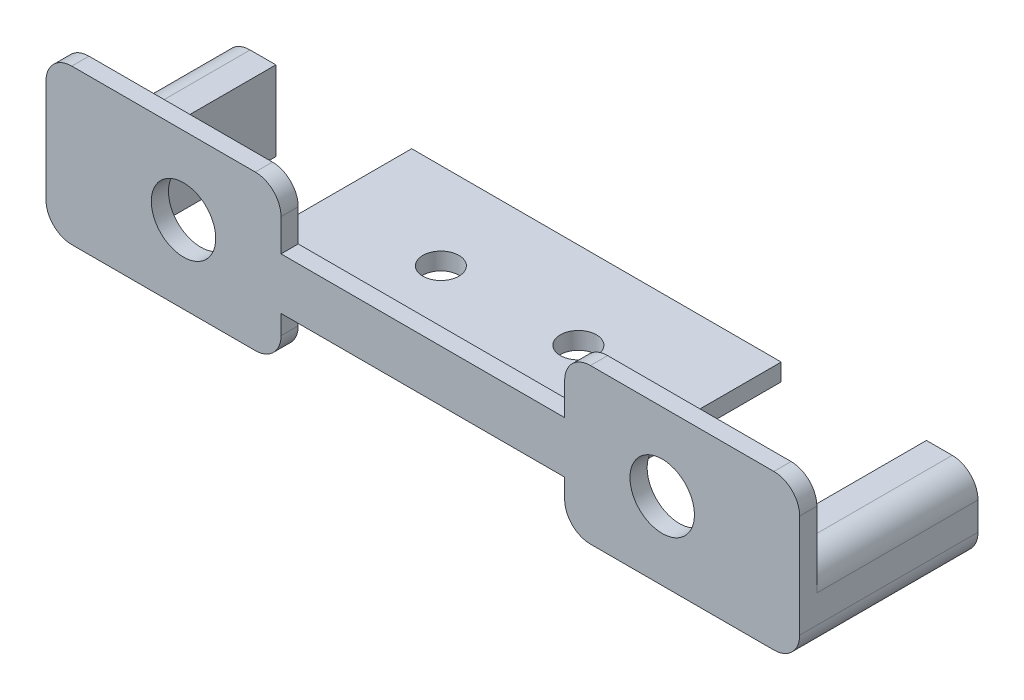
SolidWorks part; units mm, degrees
ref_plane "Front Plane" through (0, 0, 0) normal (0, 0, 1) x (1, 0, 0)
ref_plane "Top Plane" through (0, 0, 0) normal (0, 1, 0) x (1, 0, 0)
ref_plane "Right Plane" through (0, 0, 0) normal (1, 0, 0) x (0, 0, -1)
sketch "Sketch3" plane through (0, 0, 0) normal (0, 1, 0) x (1, 0, 0)
  line L1 (-21.5, 0) -> (21.5, 0)
  line L2 (-21.5, 0) -> (-21.5, 18.2)
  line L3 (-21.5, 18.2) -> (21.5, 18.2)
  line L4 (21.5, 0) -> (21.5, 18.2)
  line L5 (-8, 8.1) -> (8, 8.1) construction
  circle A0 centre (-8, 8.1) radius 2.1
  circle A1 centre (8, 8.1) radius 2.1
  point P6 (0, 0)
  point P12 (0, 8.1)
  dimension "D2" = 4.2
  dimension "D1" = 16
  dimension "D3" = 8
  dimension "D4" = 6
  dimension "D5" = 43
extrude "Boss-Extrude5" add sketch "Sketch3" against normal blind 2 separate body
sketch "Sketch1" plane through (0, 0, 0) normal (0, 0, 1) x (1, 0, 0)
  line L0 (0, -1000) -> (0, 49000) construction
  line L1 (-43.85, -9.25) -> (-16.5, -9.25)
  line L2 (-43.85, -9.25) -> (-43.85, 8.75)
  line L4 (43.85, -9.25) -> (43.85, 8.75)
  line L5 (-43.85, -0.25) -> (43.85, -0.25) construction
  line L6 (-43.85, 8.75) -> (-16.5, 8.75)
  line L15 (-37.85, -24) -> (-37.85, 0) construction
  line L16 (-16.5, 8.75) -> (-16.5, 2)
  line L17 (-16.5, -9.25) -> (-16.5, -4)
  line L18 (-16.5, -4) -> (16.5, -4)
  line L19 (16.5, -4) -> (16.5, -9.25)
  line L20 (16.5, -9.25) -> (43.85, -9.25)
  line L21 (-16.5, 2) -> (16.5, 2)
  line L22 (-21.5, -2) -> (21.5, -2) construction
  line L23 (-21.5, 0) -> (21.5, 0) construction
  line L24 (-21.5, -2) -> (-21.5, 0) construction
  line L25 (16.5, 2) -> (16.5, 8.75)
  line L26 (16.5, 8.75) -> (43.85, 8.75)
  circle A0 centre (-27.85, -0.25) radius 3.75
  circle A2 centre (27.85, -0.25) radius 3.75
  point P14 (0, -4)
  point P28 (-16.5, 1.9721)
  point P31 (-17.976, 1.614)
  point P32 (0, 2)
  dimension "D3" = 7.5
  dimension "D4" = 10
  dimension "D1" = 18
  dimension "D2" = 6
  dimension "D5" = 5
  dimension "D6" = 2
  dimension "D7" = 4
  dimension "D8" = 5
  dimension "D9" = 2
extrude "Boss-Extrude1" add sketch "Sketch1" along normal blind 2
chamfer "Chamfer1" distance 1.5 angle 45 1 edges at (0, -2, 0)
sketch "Sketch5" plane through (0, 0, 0) normal (0, 0, -1) x (-1, 0, 0)
  line L0 (43.85, -9.25) -> (16.5, -9.25) construction
  line L1 (43.85, 0) -> (37.85, 0)
  line L2 (43.85, 0) -> (43.85, -9.25)
  line L3 (43.85, -9.25) -> (37.85, -9.25)
  line L4 (37.85, 0) -> (37.85, -9.25)
  line L5 (37.85, -24) -> (37.85, 0) construction
  line L6 (37.85, 0) -> (60.85, 0) construction
extrude "Boss-Extrude4" add sketch "Sketch5" along normal up to surface (18.75 mm away)
mirror "Mirror2" about plane through (0, 0, 0) normal (1, 0, 0) of "Boss-Extrude4"
fillet "Fillet1" radius 3 10 edges at (-43.85, -9.25, -8.375) (-43.85, 8.75, 1) (-43.85, 0, -9.375) (43.85, 0, -9.375) (43.85, -9.25, -8.375) (43.85, 8.75, 1) (16.5, -9.25, 1) (16.5, 8.75, 1) (-16.5, 8.75, 1) (-16.5, -9.25, 1)
equation "\"width\"= 24"
equation "\"thk\"= 3"
equation "\"holesize\"= 4.2"
equation "\"holedistance\"= ( 20 + 12 ) / 2"
equation "\"threaded_hole\"= 3.9"
equation "\"fillet_radius\"= 2"
equation "\"ground_clearance\"= 25"
equation "\"tire_thk\"= 3"
equation "\"innerwheel_diam\" = \"wheel_diam\"-2*\"tire_thk\""
equation "\"innerwheel_thk\"= 8"
equation "\"wheel_diam\"= 2*(\"width\"/2+\"ground_clearance\")"
equation "\"coloursensor_holesize\"= 2.65"
equation "\"hole_to_edge\" = 4"
equation "\"D1@Sketch3\"=\"holedistance\""
equation "\"D2@Sketch3\"=\"holesize\""
